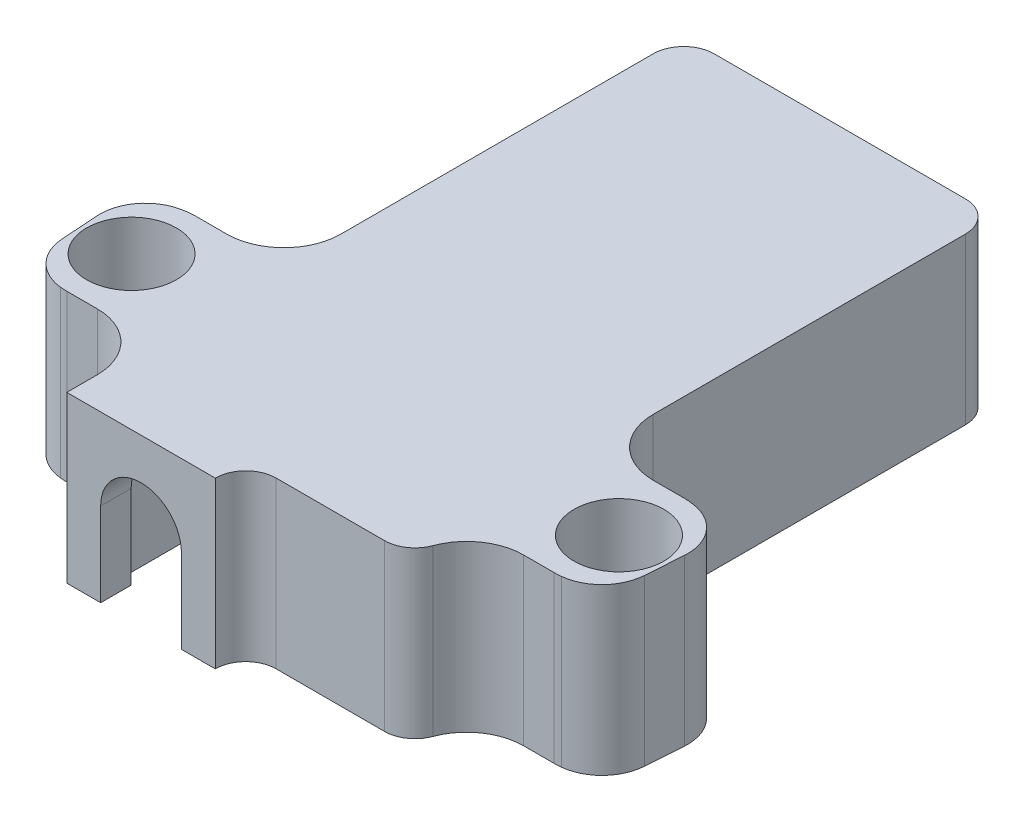
SolidWorks part; units mm, degrees
ref_plane "Front Plane" through (0, 0, 0) normal (0, 0, 1) x (1, 0, 0)
ref_plane "Top Plane" through (0, 0, 0) normal (0, 1, 0) x (1, 0, 0)
ref_plane "Right Plane" through (0, 0, 0) normal (1, 0, 0) x (0, 0, -1)
sketch "Sketch1" plane through (0, 0, 0) normal (0, 1, 0) x (1, 0, 0)
  line L0 (-24.2603, 0) -> (21.0129, 0) construction
  line L1 (0, 32.3789) -> (0, -20.9174) construction
  line L2 (0, 30.5) -> (0, -8) construction
  line L3 (-10.25, 30.5) -> (10.25, 30.5)
  line L4 (-10.25, 30.5) -> (-10.25, -8)
  line L5 (-10.25, -8) -> (10.25, -8)
  line L6 (10.25, 30.5) -> (10.25, -8)
  line L7 (-16, 4.25) -> (-10.25, 4.25)
  line L8 (-16, -4.25) -> (-10.25, -4.25)
  line L9 (16, 4.25) -> (10.25, 4.25)
  line L10 (16, -4.25) -> (10.25, -4.25)
  circle A0 centre (-16, 0) radius 1.75
  circle A1 centre (16, 0) radius 1.75
  circle A2 centre (-16, 0) radius 4.25
  circle A3 centre (16, 0) radius 4.25
  dimension "D1" = 3.5
  dimension "D2" = 32
  dimension "D3" = 20.5
  dimension "D5" = 8
  dimension "D6" = 38.5
  dimension "D4" = 2.5
extrude "Boss-Extrude1" add sketch "Sketch1" along normal blind 1.5 contours L6 L3 L4 L5 | A2 L8 L4 L7 | A2 A0 | L10 A3 L9 L6 | A3 A1
sketch "Sketch2" plane through (0, 1.5, 0) normal (0, 1, 0) x (1, 0, 0)
  line L1 (-10.25, 30.5) -> (10.25, 30.5)
  line L2 (-10.25, 30.5) -> (-10.25, -8)
  line L3 (-10.25, -8) -> (10.25, -8)
  line L4 (10.25, 30.5) -> (10.25, -8)
extrude "Boss-Extrude2" add sketch "Sketch2" along normal offset from surface (7.35 mm away) 8.85 up to face at (0, 0, -3.75)
sketch "Sketch3" plane through (0, 0, 0) normal (0, -1, 0) x (1, 0, 0)
  line L0 (-10.25, 8) -> (10.25, 8) construction
  line L1 (-8.75, 6.5) -> (8.75, 6.5)
  line L2 (-8.75, 6.5) -> (-8.75, -29)
  line L3 (-8.75, -29) -> (8.75, -29)
  line L4 (8.75, 6.5) -> (8.75, -29)
  line L5 (-10.25, -30.5) -> (10.25, -30.5) construction
  line L6 (-10.25, -30.5) -> (-10.25, -4.25) construction
  line L7 (10.25, -30.5) -> (10.25, -4.25) construction
  line L8 (-8.75, 6.5) -> (-8.75, 8)
  line L9 (-2, 6.5) -> (-2, 8)
  line M8 (10.25, 8) -> (-10.25, 8)
  dimension "D1" = 1.5
  dimension "D2" = 1.5
  dimension "D3" = 1.5
  dimension "D4" = 1.5
  dimension "D5" = 6.75
extrude "Cut-Extrude1" cut sketch "Sketch3" against normal offset from surface (7.35 mm away) 1.5 contours L4 L1 L2 L3 | L1 L9 L8 M8 up to face at (0, 8.85, -11.25)
sketch "Sketch4" plane through (0, 0, 0) normal (0, -1, 0) x (1, 0, 0)
  line L0 (-6.45, -29) -> (-6.45, -30.5)
  line L1 (-8.75, -29) -> (8.75, -29) construction
  line L2 (-10.25, -30.5) -> (10.25, -30.5) construction
  line L3 (0.75, -29) -> (0.75, -30.5)
  line L4 (-8.75, 8) -> (-8.75, -29) construction
  line L5 (-6.45, -29) -> (0.75, -29)
  line L6 (-6.45, -30.5) -> (0.75, -30.5)
  dimension "D1" = 2.3
  dimension "D2" = 7.2
extrude "Cut-Extrude2" cut sketch "Sketch4" against normal offset from surface (4.05 mm away) 3.3 up to face at (-0.6667, 7.35, -4.8333)
sketch "Sketch6" plane through (0, 7.35, 0) normal (0, -1, 0) x (1, 0, 0)
  line L0 (8.75, 6.5) -> (8.75, -29) construction
  line L1 (-8.75, -29) -> (8.75, -29)
  line L2 (-8.75, -29) -> (-8.75, -27.5)
  line L3 (-8.75, -27.5) -> (8.75, -27.5)
  line L4 (8.75, -29) -> (8.75, -27.5)
  dimension "D1" = 1.5
extrude "Boss-Extrude3" add sketch "Sketch6" along normal blind 1.35
sketch "Sketch7" plane through (0, 0, -29) normal (0, 0, 1) x (1, 0, 0)
  line L0 (8.75, 6) -> (8.75, 0) construction
  line L1 (8.75, 4.25) -> (5.25, 4.25)
  line L2 (8.75, 4.25) -> (8.75, 2.25)
  line L3 (8.75, 2.25) -> (5.25, 2.25)
  line L4 (5.25, 4.25) -> (5.25, 2.25)
  line L5 (-8.75, 6) -> (8.75, 6) construction
  dimension "D1" = 1.75
  dimension "D2" = 3.5
  dimension "D3" = 2
extrude "Boss-Extrude4" add sketch "Sketch7" along normal blind 1
sketch "Sketch8" plane through (0, 1.5, 0) normal (0, 1, 0) x (1, 0, 0)
  line L3 (-10.25, -4.25) -> (-10.25, 4.25)
  line L4 (-10.25, 4.25) -> (-16, 4.25)
  line L5 (-16, -4.25) -> (-10.25, -4.25)
  line L6 (-10.25, -4.25) -> (-10.25, 4.25)
  line L7 (-10.25, 4.25) -> (-16, 4.25)
  line L8 (-16, -4.25) -> (-10.25, -4.25)
  line L9 (10.25, 4.25) -> (10.25, -4.25)
  line L10 (10.25, -4.25) -> (16, -4.25)
  line L11 (16, 4.25) -> (10.25, 4.25)
  line L12 (10.25, 4.25) -> (10.25, -4.25)
  line L13 (10.25, -4.25) -> (16, -4.25)
  line L14 (16, 4.25) -> (10.25, 4.25)
  circle A0 centre (-16, 0) radius 2.95
  circle A1 centre (16, 0) radius 2.95
  arc A5 (-16, 4.25) -> (-16, -4.25) centre (-16, 0) ccw
  arc A8 (-16, 4.25) -> (-16, -4.25) centre (-16, 0) ccw
  arc A11 (16, -4.25) -> (16, 4.25) centre (16, 0) ccw
  arc A14 (16, -4.25) -> (16, 4.25) centre (16, 0) ccw
  dimension "D1" = 5.9
  dimension "D2" = 0
  dimension "D3" = 0
extrude "Boss-Extrude5" add sketch "Sketch8" along normal up to surface (7.35 mm away)
fillet "Fillet2" radius 3.75 4 edges
sketch "Sketch9" plane through (0, 8.85, 0) normal (0, 1, 0) x (1, 0, 0)
  line L0 (-24.9829, 53.6863) -> (-20.9528, -3.9479)
  line L1 (-15.1854, -10.3533) -> (-1.2155, -12.8165)
  line L2 (1.2155, -12.8165) -> (15.1854, -10.3533)
  line L3 (20.9528, -3.9479) -> (24.9829, 53.6863)
  line L4 (25, 54.1746) -> (25, 107.8254)
  line L5 (24.9829, 108.3137) -> (20.9528, 165.9479)
  line L6 (15.1854, 172.3533) -> (1.2155, 174.8165)
  line L7 (-1.2155, 174.8165) -> (-15.1854, 172.3533)
  line L8 (-20.9528, 165.9479) -> (-24.9829, 108.3137)
  line L9 (-25, 107.8254) -> (-25, 54.1746)
  line L10 (-18.9576, 165.8084) -> (-22.9878, 108.1742)
  line L11 (-23, 107.8254) -> (-23, 54.1746)
  line L12 (-22.9878, 53.8258) -> (-18.9576, -3.8084)
  line L13 (-14.8381, -8.3836) -> (-0.8682, -10.8469)
  line L14 (0.8682, -10.8469) -> (14.8381, -8.3836)
  line L15 (18.9576, -3.8084) -> (22.9878, 53.8258)
  line L16 (23, 54.1746) -> (23, 107.8254)
  line L17 (22.9878, 108.1742) -> (18.9576, 165.8084)
  line L18 (14.8381, 170.3836) -> (0.8682, 172.8469)
  line L19 (-0.8682, 172.8469) -> (-14.8381, 170.3836)
  line L20 (-18.9576, 165.8084) -> (-22.9878, 108.1742)
  line L21 (-23, 107.8254) -> (-23, 54.1746)
  line L22 (-22.9878, 53.8258) -> (-18.9576, -3.8084)
  line L23 (-14.8381, -8.3836) -> (-0.8682, -10.8469)
  line L24 (0.8682, -10.8469) -> (14.8381, -8.3836)
  line L25 (18.9576, -3.8084) -> (22.9878, 53.8258)
  line L26 (23, 54.1746) -> (23, 107.8254)
  line L27 (22.9878, 108.1742) -> (18.9576, 165.8084)
  line L28 (14.8381, 170.3836) -> (0.8682, 172.8469)
  line L29 (-0.8682, 172.8469) -> (-14.8381, 170.3836)
  arc A0 (-20.9528, -3.9479) -> (-15.1854, -10.3533) centre (-13.9698, -3.4596) ccw
  arc A1 (-1.2155, -12.8165) -> (1.2155, -12.8165) centre (0, -5.9229) ccw
  arc A2 (15.1854, -10.3533) -> (20.9528, -3.9479) centre (13.9698, -3.4596) ccw
  arc A3 (24.9829, 53.6863) -> (25, 54.1746) centre (18, 54.1746) ccw
  arc A4 (25, 107.8254) -> (24.9829, 108.3137) centre (18, 107.8254) ccw
  arc A5 (20.9528, 165.9479) -> (15.1854, 172.3533) centre (13.9698, 165.4596) ccw
  arc A6 (1.2155, 174.8165) -> (-1.2155, 174.8165) centre (0, 167.9229) ccw
  arc A7 (-15.1854, 172.3533) -> (-20.9528, 165.9479) centre (-13.9698, 165.4596) ccw
  arc A8 (-24.9829, 108.3137) -> (-25, 107.8254) centre (-18, 107.8254) ccw
  arc A9 (-25, 54.1746) -> (-24.9829, 53.6863) centre (-18, 54.1746) ccw
  arc A10 (-14.8381, 170.3836) -> (-18.9576, 165.8084) centre (-13.9698, 165.4596) ccw
  arc A11 (-22.9878, 108.1742) -> (-23, 107.8254) centre (-18, 107.8254) ccw
  arc A12 (-23, 54.1746) -> (-22.9878, 53.8258) centre (-18, 54.1746) ccw
  arc A13 (-18.9576, -3.8084) -> (-14.8381, -8.3836) centre (-13.9698, -3.4596) ccw
  arc A14 (-0.8682, -10.8469) -> (0.8682, -10.8469) centre (0, -5.9229) ccw
  arc A15 (14.8381, -8.3836) -> (18.9576, -3.8084) centre (13.9698, -3.4596) ccw
  arc A16 (22.9878, 53.8258) -> (23, 54.1746) centre (18, 54.1746) ccw
  arc A17 (23, 107.8254) -> (22.9878, 108.1742) centre (18, 107.8254) ccw
  arc A18 (18.9576, 165.8084) -> (14.8381, 170.3836) centre (13.9698, 165.4596) ccw
  arc A19 (0.8682, 172.8469) -> (-0.8682, 172.8469) centre (0, 167.9229) ccw
  arc A20 (-14.8381, 170.3836) -> (-18.9576, 165.8084) centre (-13.9698, 165.4596) ccw
  arc A21 (-22.9878, 108.1742) -> (-23, 107.8254) centre (-18, 107.8254) ccw
  arc A22 (-23, 54.1746) -> (-22.9878, 53.8258) centre (-18, 54.1746) ccw
  arc A23 (-18.9576, -3.8084) -> (-14.8381, -8.3836) centre (-13.9698, -3.4596) ccw
  arc A24 (-0.8682, -10.8469) -> (0.8682, -10.8469) centre (0, -5.9229) ccw
  arc A25 (14.8381, -8.3836) -> (18.9576, -3.8084) centre (13.9698, -3.4596) ccw
  arc A26 (22.9878, 53.8258) -> (23, 54.1746) centre (18, 54.1746) ccw
  arc A27 (23, 107.8254) -> (22.9878, 108.1742) centre (18, 107.8254) ccw
  arc A28 (18.9576, 165.8084) -> (14.8381, 170.3836) centre (13.9698, 165.4596) ccw
  arc A29 (0.8682, 172.8469) -> (-0.8682, 172.8469) centre (0, 167.9229) ccw
  dimension "D1" = 0
  dimension "D2" = 2
extrude "Cut-Extrude4" cut sketch "Sketch9" against normal up to next
fillet "Fillet5" radius 3 4 edges at (19.0145, 4.425, 2.9959) (19.4021, 4.425, -2.5472) (-19.0145, 4.425, 2.9959) (-19.4021, 4.425, -2.5472)
sketch "Sketch10" plane through (0, 0, 0) normal (0, 1, 0) x (1, 0, 0)
  line L0 (-2, -6.5) -> (-2, -8) construction
  line L1 (-10.25, -8) -> (-0.5, -8)
  line L2 (-10.25, -8) -> (-10.25, -10)
  line L3 (-10.25, -10) -> (-0.5, -10)
  line L4 (-0.5, -8) -> (-0.5, -10)
  dimension "D1" = 1.5
  dimension "D2" = 2
extrude "Boss-Extrude6" add sketch "Sketch10" along normal up to surface (8.85 mm away) up to face at (-16, 8.85, 2.95)
sketch "Sketch11" plane through (0, 0, 10) normal (0, 0, 1) x (1, 0, 0)
  line L0 (-5.375, 8.85) -> (-5.375, 0) construction
  line L1 (-10.25, 8.85) -> (-0.5, 8.85) construction
  line L2 (-10.25, 0) -> (-0.5, 0) construction
  line L3 (-2.725, 3.5) -> (-2.725, 0)
  line L4 (-8.025, 3.5) -> (-8.025, 0)
  circle A0 centre (-5.375, 3.5) radius 2.65
  line M3 (-10.25, 0) -> (-0.5, 0)
  dimension "D1" = 5.3
  dimension "D2" = 3.5
extrude "Cut-Extrude5" cut sketch "Sketch11" against normal up to next contours L0 A0 | A0 L0 | L0 A0 L4 M3 | A0 L0 L3 M3
fillet "Fillet4" radius 2 4 edges at (10.25, 4.425, 8) (10.25, 4.425, -30.5) (-10.25, 4.425, -30.5)
sketch "Sketch12" plane through (0, 0, 0) normal (0, -1, 0) x (1, 0, 0)
  line L10 (8.609, 8) -> (1.5, 8)
  line L11 (8.609, 8) -> (1.5, 8)
  line L12 (-10.25, -8) -> (-10.25, -28.5)
  line L13 (-8.25, -30.5) -> (-6.45, -30.5)
  line L14 (-0.5, 10) -> (-2.725, 10)
  line L15 (-0.5, 10) -> (-2.725, 10)
  line L16 (-2.725, 10) -> (-2.725, 8)
  line L17 (-2.725, 10) -> (-2.725, 8)
  line L21 (8.75, -29) -> (0.75, -29)
  line L22 (0.75, -29) -> (0.75, -30.5)
  line L23 (0.75, -30.5) -> (8.25, -30.5)
  line L24 (10.25, -28.5) -> (10.25, -8)
  line L25 (14, -4.25) -> (16, -4.25)
  line L26 (19.2941, -1.0038) -> (19.1224, 1.4525)
  line L27 (16, 4.25) -> (14, 4.25)
  line L29 (-2.725, 8) -> (-2, 8)
  line L30 (-2.725, 8) -> (-2, 8)
  line L31 (-2, 8) -> (-2, 6.5)
  line L32 (-2, 8) -> (-2, 6.5)
  line L33 (-2, 6.5) -> (8.75, 6.5)
  line L34 (-2, 6.5) -> (8.75, 6.5)
  line L35 (8.75, -29) -> (0.75, -29)
  line L36 (0.75, -29) -> (0.75, -30.5)
  line L37 (0.75, -30.5) -> (8.25, -30.5)
  line L38 (10.25, -28.5) -> (10.25, -8)
  line L39 (14, -4.25) -> (16, -4.25)
  line L40 (19.2941, -1.0038) -> (19.1224, 1.4525)
  line L41 (16, 4.25) -> (14, 4.25)
  line L42 (-6.45, -30.5) -> (-6.45, -29)
  line L43 (-6.45, -29) -> (-8.75, -29)
  line L44 (-8.75, -29) -> (-8.75, 8)
  line L45 (-8.75, 8) -> (-8.025, 8)
  line L46 (-8.025, 8) -> (-8.025, 10)
  line L47 (-8.025, 10) -> (-10.25, 10)
  line L48 (-10.25, 10) -> (-10.25, 8)
  line L49 (-14, 4.25) -> (-16, 4.25)
  line L50 (-19.1224, 1.4525) -> (-19.2941, -1.0038)
  line L51 (-16, -4.25) -> (-14, -4.25)
  line L52 (-10.25, -8) -> (-10.25, -28.5)
  line L53 (-8.25, -30.5) -> (-6.45, -30.5)
  line L54 (-6.45, -30.5) -> (-6.45, -29)
  line L55 (-6.45, -29) -> (-8.75, -29)
  line L56 (-8.75, -29) -> (-8.75, 8)
  line L57 (-8.75, 8) -> (-8.025, 8)
  line L58 (-8.025, 8) -> (-8.025, 10)
  line L59 (-8.025, 10) -> (-10.25, 10)
  line L60 (-10.25, 10) -> (-10.25, 8)
  line L61 (-14, 4.25) -> (-16, 4.25)
  line L62 (-19.1224, 1.4525) -> (-19.2941, -1.0038)
  line L63 (-16, -4.25) -> (-14, -4.25)
  line L64 (8.75, 6.5) -> (8.75, -29)
  line L65 (8.75, 6.5) -> (8.75, -29)
  circle A0 centre (16, 0) radius 1.75 construction
  circle A1 centre (16, 0) radius 1.75
  circle A2 centre (-16, 0) radius 1.75 construction
  circle A3 centre (-16, 0) radius 1.75
  arc A7 (-10.25, -28.5) -> (-8.25, -30.5) centre (-8.25, -28.5) ccw
  arc A8 (-14, 4.25) -> (-10.25, 8) centre (-14, 8) ccw
  arc A9 (10.4842, 6.6957) -> (14, 4.25) centre (14, 8) ccw
  arc A12 (8.25, -30.5) -> (10.25, -28.5) centre (8.25, -28.5) ccw
  arc A13 (14, -4.25) -> (10.25, -8) centre (14, -8) ccw
  arc A14 (16, -4.25) -> (17.0249, -4.1246) centre (16, 0) ccw
  arc A15 (17.0249, -4.1246) -> (19.2941, -1.0038) centre (16.3015, -1.2131) ccw
  arc A16 (19.1224, 1.4525) -> (16.4409, 4.2271) centre (16.1297, 1.2433) ccw
  arc A17 (16.4409, 4.2271) -> (16, 4.25) centre (16, 0) ccw
  arc A18 (10.4842, 6.6957) -> (14, 4.25) centre (14, 8) ccw
  arc A21 (8.25, -30.5) -> (10.25, -28.5) centre (8.25, -28.5) ccw
  arc A22 (14, -4.25) -> (10.25, -8) centre (14, -8) ccw
  arc A23 (16, -4.25) -> (17.0249, -4.1246) centre (16, 0) ccw
  arc A24 (17.0249, -4.1246) -> (19.2941, -1.0038) centre (16.3015, -1.2131) ccw
  arc A25 (19.1224, 1.4525) -> (16.4409, 4.2271) centre (16.1297, 1.2433) ccw
  arc A26 (16.4409, 4.2271) -> (16, 4.25) centre (16, 0) ccw
  arc A27 (-16, 4.25) -> (-16.4409, 4.2271) centre (-16, 0) ccw
  arc A28 (-16.4409, 4.2271) -> (-19.1224, 1.4525) centre (-16.1297, 1.2433) ccw
  arc A29 (-19.2941, -1.0038) -> (-17.0249, -4.1246) centre (-16.3015, -1.2131) ccw
  arc A30 (-17.0249, -4.1246) -> (-16, -4.25) centre (-16, 0) ccw
  arc A31 (-10.25, -8) -> (-14, -4.25) centre (-14, -8) ccw
  arc A32 (-10.25, -28.5) -> (-8.25, -30.5) centre (-8.25, -28.5) ccw
  arc A33 (-14, 4.25) -> (-10.25, 8) centre (-14, 8) ccw
  arc A34 (-16, 4.25) -> (-16.4409, 4.2271) centre (-16, 0) ccw
  arc A35 (-16.4409, 4.2271) -> (-19.1224, 1.4525) centre (-16.1297, 1.2433) ccw
  arc A36 (-19.2941, -1.0038) -> (-17.0249, -4.1246) centre (-16.3015, -1.2131) ccw
  arc A37 (-17.0249, -4.1246) -> (-16, -4.25) centre (-16, 0) ccw
  arc A38 (-10.25, -8) -> (-14, -4.25) centre (-14, -8) ccw
  arc A41 (10.4842, 6.6957) -> (8.609, 8) centre (8.609, 6) ccw
  arc A42 (10.4842, 6.6957) -> (8.609, 8) centre (8.609, 6) ccw
  arc A43 (-0.5, 10) -> (1.5, 8) centre (1.5, 10) ccw
  arc A44 (-0.5, 10) -> (1.5, 8) centre (1.5, 10) ccw
  dimension "D1" = 0
  dimension "D2" = 0
extrude "Boss-Extrude7" add sketch "Sketch12" along normal blind 2
